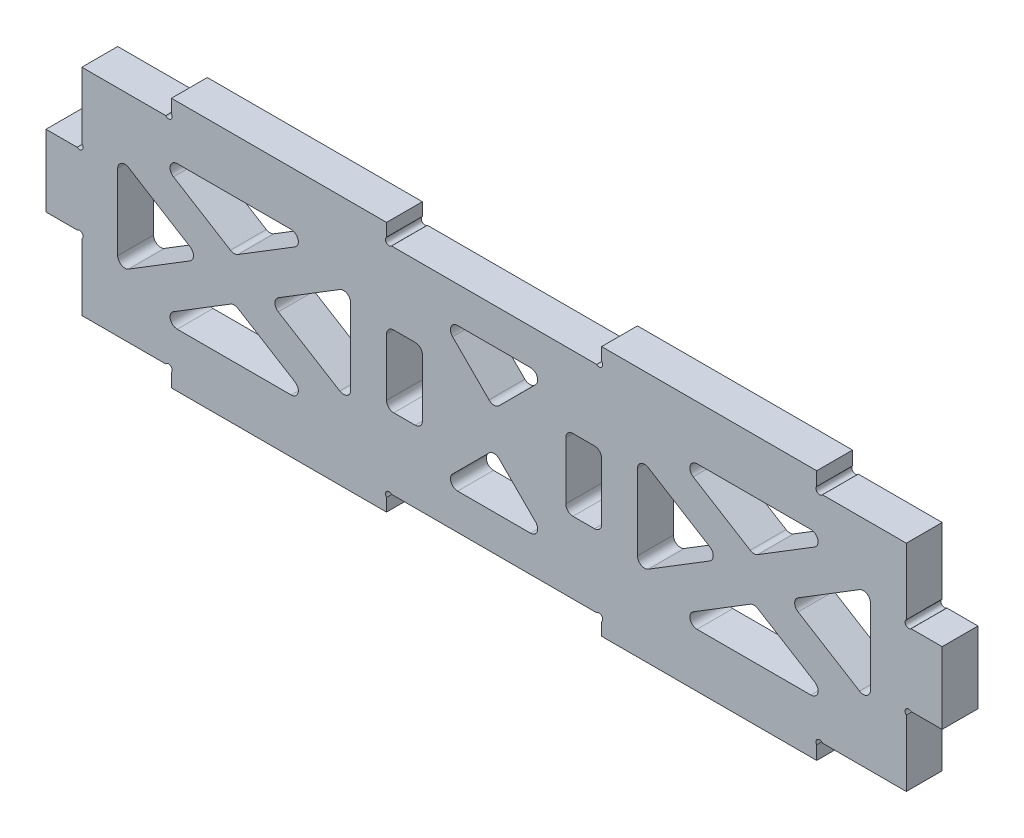
SolidWorks part; units mm, degrees
material "7050-T73510"
ref_plane "Front Plane" through (0, 0, 0) normal (0, 0, 1) x (1, 0, 0)
ref_plane "Top Plane" through (0, 0, 0) normal (0, 1, 0) x (1, 0, 0)
ref_plane "Right Plane" through (0, 0, 0) normal (1, 0, 0) x (0, 0, -1)
sketch "Sketch1" plane through (0, 0, 0) normal (0, 0, 1) x (1, 0, 0)
  line L1 (-158.75, -38.1) -> (158.75, -38.1)
  line L2 (-158.75, -38.1) -> (-158.75, 38.1)
  line L3 (-158.75, 38.1) -> (158.75, 38.1)
  line L4 (158.75, -38.1) -> (158.75, 38.1)
  line L5 (-158.75, -38.1) -> (158.75, 38.1) construction
  line L6 (-158.75, 38.1) -> (158.75, -38.1) construction
  point P0 (0, 0)
  dimension "D1" = 317.5
  dimension "D2" = 76.2
extrude "Boss-Extrude1" add sketch "Sketch1" along normal blind 12.7 contours L1 L3 region at (0, 0, 0)
sketch "Sketch2" plane through (0, 0, 12.7) normal (0, 0, 1) x (1, 0, 0)
  line L0 (-158.75, -38.1) -> (158.75, -38.1) construction
  line L1 (-38.1, -38.1) -> (-114.3, -38.1)
  line L2 (-38.1, -38.1) -> (-38.1, -44.45)
  line L3 (-38.1, -44.45) -> (-114.3, -44.45)
  line L4 (-114.3, -38.1) -> (-114.3, -44.45)
  line L5 (0, -55) -> (0, 55) construction
  line L6 (38.1, -44.45) -> (114.3, -44.45)
  line L7 (114.3, -38.1) -> (114.3, -44.45)
  line L8 (38.1, -38.1) -> (114.3, -38.1)
  line L9 (38.1, -38.1) -> (38.1, -44.45)
  line L10 (55, 0) -> (-55, 0) construction
  line L11 (38.1, 38.1) -> (38.1, 44.45)
  line L12 (38.1, 38.1) -> (114.3, 38.1)
  line L13 (114.3, 38.1) -> (114.3, 44.45)
  line L14 (38.1, 44.45) -> (114.3, 44.45)
  line L15 (-38.1, 44.45) -> (-114.3, 44.45)
  line L16 (-114.3, 38.1) -> (-114.3, 44.45)
  line L17 (-38.1, 38.1) -> (-114.3, 38.1)
  line L18 (-38.1, 38.1) -> (-38.1, 44.45)
  point P12 (-38.1, -41.275)
  dimension "D1" = 76.2
  dimension "D2" = 6.35
  dimension "D3" = 76.2
extrude "Boss-Extrude2" add sketch "Sketch2" against normal blind 12.7
sketch "Sketch3" plane through (0, 0, 12.7) normal (0, 0, 1) x (1, 0, 0)
  line L0 (6.985, 0) -> (-6.985, 0) construction
  line L1 (-158.75, -38.1) -> (-146.05, -38.1)
  line L2 (-158.75, -38.1) -> (-158.75, -12.7)
  line L3 (-158.75, -12.7) -> (-146.05, -12.7)
  line L4 (-146.05, -38.1) -> (-146.05, -12.7)
  line L6 (-158.75, 12.7) -> (-146.05, 12.7)
  line L7 (-146.05, 38.1) -> (-146.05, 12.7)
  line L8 (-158.75, 38.1) -> (-146.05, 38.1)
  line L9 (-158.75, 38.1) -> (-158.75, 12.7)
  line L10 (0, -6.985) -> (0, 6.985) construction
  line L11 (158.75, 38.1) -> (158.75, 12.7)
  line L12 (158.75, 38.1) -> (146.05, 38.1)
  line L13 (146.05, 38.1) -> (146.05, 12.7)
  line L14 (158.75, 12.7) -> (146.05, 12.7)
  line L15 (158.75, -12.7) -> (146.05, -12.7)
  line L16 (146.05, -38.1) -> (146.05, -12.7)
  line L17 (158.75, -38.1) -> (146.05, -38.1)
  line L18 (158.75, -38.1) -> (158.75, -12.7)
  line L19 (25.4, 12.7) -> (38.1, 12.7)
  line L20 (25.4, 12.7) -> (25.4, -12.7)
  line L21 (25.4, -12.7) -> (38.1, -12.7)
  line L22 (38.1, 12.7) -> (38.1, -12.7)
  line L23 (-38.1, -38.1) -> (38.1, -38.1) construction
  line L24 (-25.4, -12.7) -> (-38.1, -12.7)
  line L25 (-38.1, 12.7) -> (-38.1, -12.7)
  line L26 (-25.4, 12.7) -> (-38.1, 12.7)
  line L27 (-25.4, 12.7) -> (-25.4, -12.7)
  line L28 (-38.1, 38.1) -> (38.1, 38.1) construction
  dimension "D1" = 25.4
  dimension "D2" = 12.7
  dimension "D3" = 50.8
  dimension "D4" = 12.7
  dimension "D5" = 25.4
  dimension "D6" = 25.4
extrude "Cut-Extrude1" cut sketch "Sketch3" against normal through all
sketch "Sketch4" plane through (0, 0, 12.7) normal (0, 0, 1) x (1, 0, 0)
  line L0 (6.985, 0) -> (-6.985, 0) construction
  line L1 (-133.35, -25.4) -> (-50.8, -25.4)
  line L2 (-133.35, -25.4) -> (-133.35, 25.4)
  line L3 (-133.35, 25.4) -> (-50.8, 25.4)
  line L4 (-50.8, -25.4) -> (-50.8, 25.4)
  line L5 (-133.35, 25.4) -> (-133.4571, 24.9525)
  line L6 (-19.05, 25.4) -> (0, 6.35)
  line L7 (-146.05, 12.7) -> (-146.05, 38.1) construction
  line L8 (-38.1, 12.7) -> (-38.1, -12.7) construction
  line L9 (-146.05, 38.1) -> (-114.3, 38.1) construction
  line L10 (-133.35, 25.4) -> (-50.8, -25.4) construction
  line L11 (-133.35, -25.4) -> (-50.8, 25.4) construction
  line L12 (-133.35, 17.944) -> (-104.1911, 0)
  line L13 (-121.2339, -25.4) -> (-92.075, -7.456)
  line L14 (-121.2339, 25.4) -> (-92.075, 7.456)
  line L15 (-133.35, -17.944) -> (-104.1911, 0)
  line L16 (0, -6.985) -> (0, 6.985) construction
  line L17 (0, 6.35) -> (19.05, 25.4)
  line L18 (-130.022, -30.808) -> (-47.472, 19.992) construction
  line L19 (0, -6.35) -> (19.05, -25.4)
  line L20 (-136.678, -19.992) -> (-54.128, 30.808) construction
  line L21 (-136.678, 19.992) -> (-54.128, -30.808) construction
  line L22 (-130.022, 30.808) -> (-47.472, -19.992) construction
  line L23 (-79.9589, 0) -> (-50.8, 17.944)
  line L24 (-92.075, -7.456) -> (-62.9161, -25.4)
  line L25 (-19.05, -25.4) -> (0, -6.35)
  line L26 (-38.1, -38.1) -> (38.1, -38.1) construction
  line L42 (-19.05, -25.4) -> (19.05, -25.4)
  line L43 (-146.05, -38.1) -> (-114.3, -38.1) construction
  line L44 (-19.05, -25.4) -> (-19.05, 25.4)
  line L45 (-19.05, 25.4) -> (19.05, 25.4)
  line L46 (19.05, -25.4) -> (19.05, 25.4)
  line L56 (-92.075, 7.456) -> (-62.9161, 25.4)
  line L57 (-79.9589, 0) -> (-50.8, -17.944)
  point P0 (-93.6625, 0)
  point P54 (0, 0)
  dimension "D1" = 12.7
  dimension "D2" = 12.7
  dimension "D3" = 12.7
  dimension "D7" = 12.7
  dimension "D10" = 12.7
  dimension "D9" = 12.7
  dimension "D8" = 38.1
  dimension "D4" = 6.35
  dimension "D5" = 6.35
sketch "Sketch7" plane through (0, 0, 12.7) normal (0, 0, 1) x (1, 0, 0)
  line L0 (0, -6.985) -> (0, 6.985) construction
  line L1 (6.985, 0) -> (-6.985, 0) construction
  circle A1 centre (-115.3222, -38.8536) radius 1.27
  circle A2 centre (-37.2199, -39.0156) radius 1.27
  circle A3 centre (37.2199, -39.0156) radius 1.27
  circle A4 centre (115.3222, -38.8536) radius 1.27
  circle A7 centre (115.3222, 38.8536) radius 1.27
  circle A8 centre (37.2199, 39.0156) radius 1.27
  circle A9 centre (-37.2199, 39.0156) radius 1.27
  circle A10 centre (-115.3222, 38.8536) radius 1.27
  circle A12 centre (-146.8896, -13.6529) radius 1.27
  circle A15 centre (-146.8896, 13.6529) radius 1.27
  circle A16 centre (146.8896, -13.6529) radius 1.27
  circle A17 centre (146.8896, 13.6529) radius 1.27
  point P29 (146.8896, 13.6529)
  dimension "D1" = 2.54
  dimension "D2" = 2.54
extrude "Cut-Extrude4" cut sketch "Sketch7" against normal through all
extrude "Cut-Extrude6" cut sketch "Sketch4" against normal through all contours L24 L13 L1 | L2 L15 L12 | L14 L56 L3 | L23 L57 L4 | L25 L42 L19 | L45 L6 L17 region at (-92.075, -19.4187, 12.7) region at (-123.6304, 0, 12.7) region at (-60.5196, 0, 12.7) region at (-92.075, 19.4187, 12.7) region at (0, 19.05, 12.7) region at (0, -19.05, 12.7)
mirror "Mirror1" about plane through (0, 0, 0) normal (1, 0, 0) of "Cut-Extrude6"
fillet "Fillet1" radius 2.54 38 edges at (-19.05, -25.4, 6.35) (-19.05, 25.4, 6.35) (-133.35, 17.944, 6.35) (-62.9161, -25.4, 6.35) (-121.2339, -25.4, 6.35) (-133.35, -17.944, 6.35) (-50.8, -17.944, 6.35) (-50.8, 17.944, 6.35) (-104.1911, 0, 6.35) (-62.9161, 25.4, 6.35) (-92.075, 7.456, 6.35) (-92.075, -7.456, 6.35) (-79.9589, 0, 6.35) (-121.2339, 25.4, 6.35) (62.9161, 25.4, 6.35) (121.2339, 25.4, 6.35) (133.35, 17.944, 6.35) (104.1911, 0, 6.35) (62.9161, -25.4, 6.35) (121.2339, -25.4, 6.35) (92.075, -7.456, 6.35) (79.9589, 0, 6.35) (50.8, 17.944, 6.35) (50.8, -17.944, 6.35) (92.075, 7.456, 6.35) (133.35, -17.944, 6.35) (19.05, -25.4, 6.35) (0, -6.35, 6.35) (19.05, 25.4, 6.35) (0, 6.35, 6.35) (38.1, -12.7, 6.35) (25.4, -12.7, 6.35) (38.1, 12.7, 6.35) (25.4, 12.7, 6.35) (-25.4, 12.7, 6.35) (-38.1, 12.7, 6.35) (-25.4, -12.7, 6.35) (-38.1, -12.7, 6.35)
